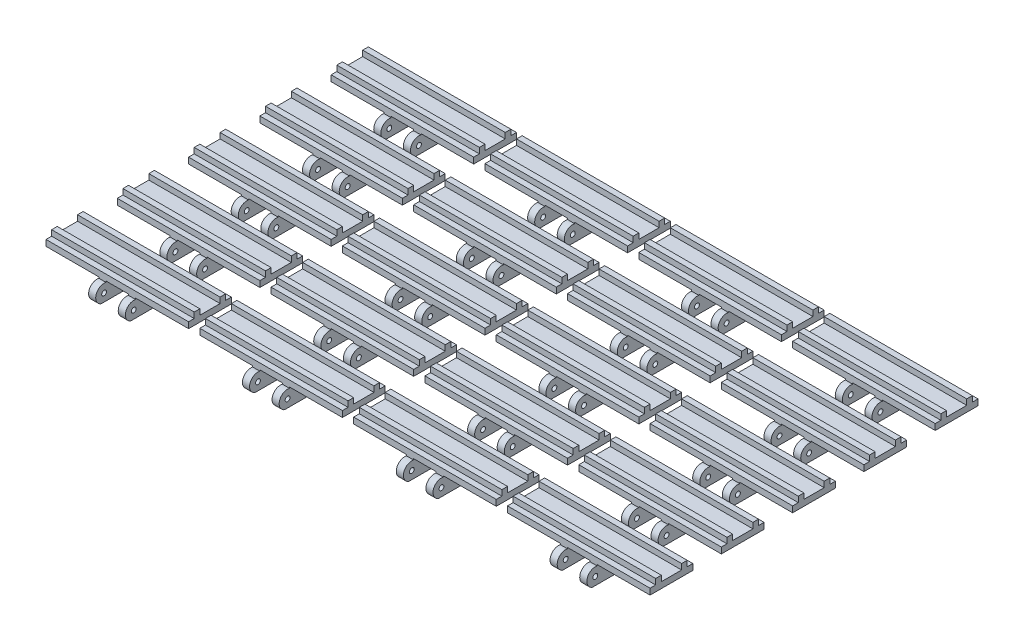
SolidWorks part; units mm, degrees
ref_plane "前视基准面" through (0, 0, 0) normal (0, 0, 1) x (1, 0, 0)
ref_plane "上视基准面" through (0, 0, 0) normal (0, 1, 0) x (1, 0, 0)
ref_plane "右视基准面" through (0, 0, 0) normal (1, 0, 0) x (0, 0, -1)
other "Configuration Table"
sketch "草图1" plane through (0, 0, 0) normal (0, 1, 0) x (1, 0, 0)
  line L0 (-3, 0) -> (3, 0) construction
  line L1 (-19, -5.7) -> (19, -5.7)
  line L2 (-19, -5.7) -> (-19, 5.7)
  line L3 (-19, 5.7) -> (19, 5.7)
  line L4 (19, -5.7) -> (19, 5.7)
  line L5 (-19, -5.7) -> (19, 5.7) construction
  line L6 (-19, 5.7) -> (19, -5.7) construction
  line L41 (-7, 7) -> (-3, 7)
  line L42 (-7, 7) -> (-7, -7)
  line L43 (-7, -7) -> (-3, -7)
  line L44 (-3, 7) -> (-3, -7)
  line L45 (3, 7) -> (7, 7)
  line L46 (3, 7) -> (3, -7)
  line L47 (3, -7) -> (7, -7)
  line L48 (7, 7) -> (7, -7)
  point P0 (0, 0)
  point P6 (0, 0)
  point P7 (0, 0)
  point P12 (0, 0)
  dimension "D1" = 38
  dimension "D2" = 11.4
  dimension "D3" = 6
  dimension "D4" = 4
  dimension "D5" = 14
extrude "凸台-拉伸1" add sketch "草图1" along normal blind 1.6 contours L2 L3 L4 L1
extrude "凸台-拉伸2" add sketch "草图1<4>" against normal blind 5 contours L48 L47 L46 L45 | L44 L43 L42 L41
sketch "草图1<4>" plane through (0, 0, 0) normal (0, 1, 0) x (1, 0, 0) same geometry as "草图1"
sketch "草图2" plane through (0, 0, 0) normal (0, 1, 0) x (1, 0, 0)
  line L1 (-5, 7) -> (5, 7)
  line L2 (-5, 7) -> (-5, 5.7)
  line L3 (-5, 5.7) -> (5, 5.7)
  line L4 (5, 7) -> (5, 5.7)
  line L5 (-7, 7) -> (-3, 7) construction
  line L6 (-19, 5.7) -> (19, 5.7) construction
  line L7 (3, 7) -> (7, 7) construction
  line L9 (-5, -7) -> (-7, -7)
  line L10 (-5, -7) -> (-5, -5.7)
  line L11 (-5, -5.7) -> (-7, -5.7)
  line L12 (-7, -7) -> (-7, -5.7)
  line L13 (-7, -7) -> (-3, -7) construction
  line L14 (-19, -5.7) -> (19, -5.7) construction
  line L17 (-7, -5.7) -> (-7, -7) construction
  line L18 (5, -7) -> (7, -7)
  line L19 (5, -7) -> (5, -5.7)
  line L20 (5, -5.7) -> (7, -5.7)
  line L21 (7, -7) -> (7, -5.7)
  line L22 (3, -7) -> (7, -7) construction
  line L23 (7, -5.7) -> (7, -7) construction
  line L25 (-5, 7) -> (-5.1, 7)
  line L26 (-5, 7) -> (-5, 5.7)
  line L27 (-5, -5.7) -> (-4.9, -5.7)
  line L28 (-5, -5.7) -> (-5, -7)
  line L29 (-5, -7) -> (-4.9, -7)
  line L30 (-4.9, -5.7) -> (-4.9, -7)
  line L31 (5, -5.7) -> (4.9, -5.7)
  line L32 (5, -5.7) -> (5, -7)
  line L33 (5, -7) -> (4.9, -7)
  line L34 (4.9, -5.7) -> (4.9, -7)
  line L35 (-5, 5.7) -> (-5.1, 5.7)
  line L36 (-5.1, 7) -> (-5.1, 5.7)
  line L37 (5, 7) -> (5.1, 7)
  line L38 (5, 7) -> (5, 5.7)
  line L39 (5, 5.7) -> (5.1, 5.7)
  line L40 (5.1, 7) -> (5.1, 5.7)
  dimension "D1" = 0.1
  dimension "D2" = 0.1
  dimension "D3" = 0.1
  dimension "D4" = 0.1
extrude "切除-拉伸1" cut sketch "草图2" against normal through all contours L25 L36 L35 L2 | L4 L1 L2 L3 | L40 L37 L4 L39 | L12 L9 L10 L11 | L30 L27 L10 L29 | L31 L34 L33 L19 | L18 L21 L20 L19 region at (0, 0, -6.35) region at (-5.05, 0, -6.35) region at (5.05, 0, -6.35) region at (-6, 0, 6.35) region at (-4.95, 0, 6.35) region at (6, 0, 6.35) region at (4.95, 0, 6.35)
sketch "草图3" plane through (0, 0, 0) normal (1, 0, 0) x (0, 0, -1)
  line L1 (-6.2, -2.5) -> (6.2, -2.5)
  circle A0 centre (-6.2, -2.5) radius 0.65
  circle A1 centre (6.2, -2.5) radius 0.55
  point P2 (0, -2.5)
  dimension "D2" = 1.3
  dimension "D3" = 1.1
  dimension "D1" = 2.5
  dimension "D4" = 12.4
sketch "草图4" plane through (0, 0, 0) normal (1, 0, 0) x (0, 0, -1)
  line L0 (-5.7, 0) -> (5.7, 0) construction
  line L6 (-5.7, 0) -> (-3.7, 0)
  line L7 (-5.7, 0) -> (-5.7, -5)
  line L8 (-5.7, -5) -> (-3.7, -5)
  line L9 (-3.7, 0) -> (-3.7, -5)
  line L10 (5.7, 0) -> (8.45, 0)
  line L11 (5.7, 0) -> (5.7, -2.5)
  line L12 (5.7, -2.5) -> (8.45, -2.5)
  line L13 (8.45, 0) -> (8.45, -2.5)
  line L14 (5.7, -5) -> (8.45, -5)
  line L15 (5.7, -5) -> (5.7, -2.5)
  line L16 (5.7, -2.5) -> (8.45, -2.5)
  line L17 (8.45, -5) -> (8.45, -2.5)
  circle A0 centre (-6.2, -2.5) radius 2.5
  circle A1 centre (6.2, -2.5) radius 2.25
  dimension "D1" = 4.5
extrude "切除-拉伸2" cut sketch "草图4" against normal up to surface (-4.9 mm away) from surface contours A0 L8 L9 | A0 region at (0, -4.4382, 4.2486) up to face at (4.9, -2.5, 6.35) starting at face at (7, -2, -1.66)
extrude "切除-拉伸3" cut sketch "草图4<3>" along normal up to surface (-4.9 mm away) from surface contours A0 L8 L9 | A0 region at (0, -4.4382, 4.2486) up to face at (-4.9, -2.5, 6.35) starting at face at (-7, -2, -1.66)
sketch "草图4<3>" plane through (0, 0, 0) normal (1, 0, 0) x (0, 0, -1) same geometry as "草图4"
extrude "切除-拉伸6" cut sketch "草图4<5>" against normal through all both and the other way through all contours A1 L13 L10 L11 | A1 L15 L14 L17 region at (0, -0.5081, -7.6) region at (0, -4.4919, -7.6)
sketch "草图4<5>" plane through (0, 0, 0) normal (1, 0, 0) x (0, 0, -1) same geometry as "草图4"
extrude "凸台-拉伸3" add sketch "草图4<6>" along normal up to surface (7 mm away) from surface contours L12 A1 L11 | L14 A1 L12 L15 region at (0, -1.5098, -6.8911) region at (0, -3.4902, -6.8911) up to face at (7, -2.2194, -1.845) starting at face at (5.1, -2.5, -6.3534)
sketch "草图4<6>" plane through (0, 0, 0) normal (1, 0, 0) x (0, 0, -1) same geometry as "草图4"
extrude "凸台-拉伸4" add sketch "草图4<7>" against normal up to surface (1.9 mm away) from surface contours L12 A1 L11 | L14 A1 L12 L15 region at (0, -1.5098, -6.8911) region at (0, -3.4902, -6.8911) up to face at (-7, -2.2194, -1.845) starting at face at (-5.1, -2.5, -6.3534)
sketch "草图4<7>" plane through (0, 0, 0) normal (1, 0, 0) x (0, 0, -1) same geometry as "草图4"
extrude "切除-拉伸7" cut sketch "草图3" against normal through all both and the other way through all contours A0 | A1
sketch "草图5" plane through (0, 0, 0) normal (1, 0, 0) x (0, 0, -1)
  line L0 (-5.7, 0) -> (5.7, 0) construction
  line L6 (6.2, -2.5) -> (3.7, -2.5)
  line L7 (6.2, -2.5) -> (6.2, -5)
  line L8 (6.2, -5) -> (3.7, -5)
  line L9 (3.7, -2.5) -> (3.7, -5)
  circle A0 centre (6.2, -2.5) radius 2.5
extrude "切除-拉伸8" cut sketch "草图5" along normal up to surface (5.1 mm away) contours A0 L9 L8 | A0 region at (0, -4.4416, -4.2584) up to face at (5.1, -2.5, -6.65)
extrude "切除-拉伸9" cut sketch "草图5<2>" against normal up to surface (5.1 mm away) contours A0 L9 L8 | A0 region at (0, -4.4416, -4.2584) up to face at (-5.1, -2.5, -6.65)
sketch "草图5<2>" plane through (0, 0, 0) normal (1, 0, 0) x (0, 0, -1) same geometry as "草图5"
sketch "草图7" plane through (0, 0, 0) normal (1, 0, 0) x (0, 0, -1)
  line L0 (-3.7, -5) -> (-7, -5) construction
  line L1 (-5.7, 0) -> (-8.45, 0)
  line L2 (-5.7, 0) -> (-5.7, -2.5)
  line L3 (-5.7, -2.5) -> (-8.45, -2.5)
  line L4 (-8.45, 0) -> (-8.45, -2.5)
  line L5 (-5.7, -2.5) -> (-8.45, -2.5)
  line L6 (-5.7, -2.5) -> (-5.7, -5)
  line L7 (-5.7, -5) -> (-8.45, -5)
  line L8 (-8.45, -2.5) -> (-8.45, -5)
  circle A0 centre (-6.2, -2.5) radius 2.25
  dimension "D1" = 4.5
extrude "切除-拉伸10" cut sketch "草图7" against normal through all both and the other way through all contours A0 L2 L1 L4 region at (0, -0.5081, 7.6)
extrude "凸台-拉伸5" add sketch "草图7<4>" along normal up to surface (1.9 mm away) from surface contours L2 A0 L3 | L3 A0 L7 L6 region at (0, -1.5098, 6.8911) region at (0, -3.4902, 6.8911) up to face at (4.9, -2.5, 6.85) starting at face at (3, -2.5, 6.85)
sketch "草图7<4>" plane through (0, 0, 0) normal (1, 0, 0) x (0, 0, -1) same geometry as "草图7"
extrude "凸台-拉伸6" add sketch "草图7<5>" against normal up to surface (1.9 mm away) from surface contours L2 A0 L3 | L3 A0 L7 L6 region at (0, -1.5098, 6.8911) region at (0, -3.4902, 6.8911) up to face at (-4.9, -2.5, 6.85) starting at face at (-3, -2.5, 6.85)
sketch "草图7<5>" plane through (0, 0, 0) normal (1, 0, 0) x (0, 0, -1) same geometry as "草图7"
extrude "切除-拉伸11" cut sketch "草图3<3>" against normal through all both and the other way through all contours A0 | A1
sketch "草图3<3>" plane through (0, 0, 0) normal (1, 0, 0) x (0, 0, -1) same geometry as "草图3"
sketch "草图9" plane through (0, 0, 0) normal (1, 0, 0) x (0, 0, -1)
  line L0 (5.7, -5) -> (-3.7, -5) construction
  line L1 (-7, -4.603) -> (8.45, -4.603)
  line L2 (-7, -4.603) -> (-7, -5)
  line L3 (-7, -5) -> (8.45, -5)
  line L4 (8.45, -4.603) -> (8.45, -5)
  arc A0 (5.7, -4.6937) -> (5.7, -0.3063) centre (6.2, -2.5) ccw construction
extrude "切除-拉伸12" cut sketch "草图9" against normal through all both and the other way through all contours L3 L4 L1 L2
sketch "草图10" plane through (0, 1.6, 0) normal (0, 1, 0) x (1, 0, 0)
  line L0 (19, -5.7) -> (19, 5.7) construction
  line L1 (-19, 2.7) -> (19, 2.7)
  line L2 (-19, 2.7) -> (-19, 4.2)
  line L3 (-19, 4.2) -> (19, 4.2)
  line L4 (19, 2.7) -> (19, 4.2)
  line L5 (-19, -4.2) -> (19, -4.2)
  line L6 (-19, -4.2) -> (-19, -2.7)
  line L7 (-19, -2.7) -> (19, -2.7)
  line L8 (19, -4.2) -> (19, -2.7)
  line L9 (-19, -5.7) -> (-19, 5.7) construction
  line L10 (0, 2.7) -> (0, -2.7)
  line L12 (-19, 5.7) -> (19, 5.7) construction
  circle A0 centre (0, 0) radius 2.5
  circle A1 centre (-7, 0) radius 2.5
  circle A2 centre (7, 0) radius 2.5
  circle A3 centre (14, 0) radius 2.5
  circle A4 centre (-14, 0) radius 2.5
  point P0 (0, 0)
  dimension "D3" = 5
  dimension "D1" = 1.5
  dimension "D2" = 1.5
  dimension "D4" = 7
  dimension "D5" = 7
  dimension "D6" = 7
  dimension "D7" = 7
extrude "凸台-拉伸7" add sketch "草图10" along normal blind 1.5 contours L1 L4 L3 L2 | L5 L8 L7 L6
fillet "圆角1" radius 1 4 edges at (4.05, -4.603, -3.7) (-4.05, -4.603, -3.7) (-5.95, -4.603, 3.7) (5.95, -4.603, 3.7)
sketch "草图11" plane through (0, 0, 0) normal (1, 0, 0) x (0, 0, -1)
  line L0 (7, -4.603) -> (-2.7, -4.603) construction
  line L1 (-5.7, 0) -> (-1, 0)
  line L2 (-5.7, 0) -> (-5.7, -4.603)
  line L3 (-5.7, -4.603) -> (-1, -4.603)
  line L4 (-1, 0) -> (-1, -4.603)
  line L6 (5.7, 0) -> (1, 0)
  line L7 (5.7, 0) -> (5.7, -4.603)
  line L8 (5.7, -4.603) -> (1, -4.603)
  line L9 (1, 0) -> (1, -4.603)
  dimension "D1" = 1
  dimension "D2" = 1
extrude "切除-拉伸13" cut sketch "草图11" against normal through all from surface contours L4 L3 L2 L1 starting at face at (-4.9, -2.5, 6.85)
extrude "切除-拉伸14" cut sketch "草图11<2>" along normal through all from surface contours L4 L3 L2 L1 starting at face at (4.9, -2.5, 6.85)
sketch "草图11<2>" plane through (0, 0, 0) normal (1, 0, 0) x (0, 0, -1) same geometry as "草图11"
extrude "切除-拉伸15" cut sketch "草图11<4>" against normal up to surface (10.2 mm away) from surface contours L9 L8 L7 L6 up to face at (-5.1, -2.5, -5.65) starting at face at (5.1, -2.5, -5.65)
sketch "草图11<4>" plane through (0, 0, 0) normal (1, 0, 0) x (0, 0, -1) same geometry as "草图11"
pattern_linear "阵列(线性)1" count 5 spacing 19 along (0, 0, 1) of bodies 156
pattern_linear "阵列(线性)2" count 4 spacing 41 along (-1, 0, 0) of bodies 172 156 157 158 159
